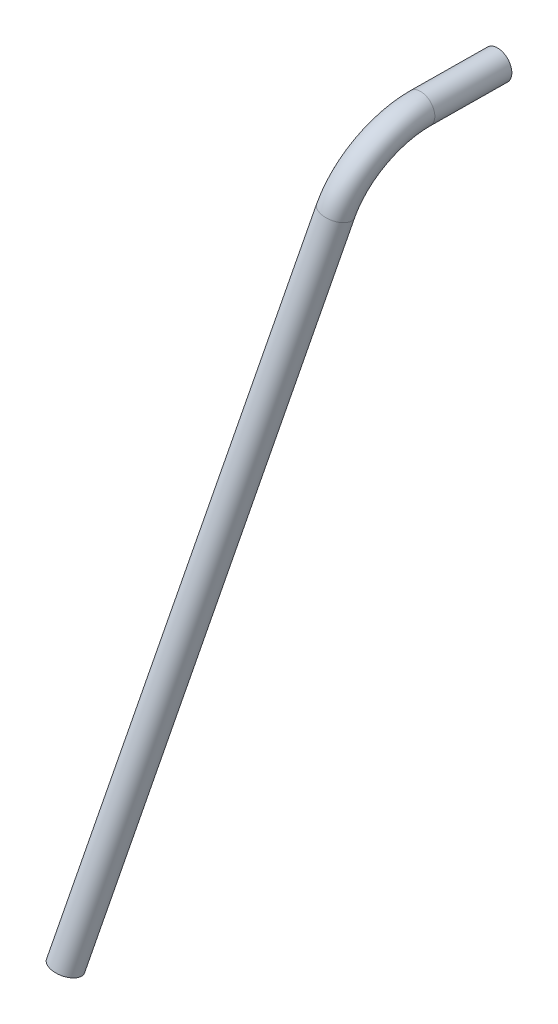
SolidWorks part; units mm, degrees
material "Silicon Rubber"
ref_plane "X-Y Datum" through (0, 0, 0) normal (0, 0, 1) x (1, 0, 0)
ref_plane "X-Z Datum" through (0, 0, 0) normal (0, 1, 0) x (1, 0, 0)
ref_plane "Y-Z Datum" through (0, 0, 0) normal (1, 0, 0) x (0, 0, -1)
sketch3d "3DSketch1"
  line L0 (224.1379, 49.8486, -283.6466) -> (167.4145, -265.9267, -205.541)
  line L1 (229.5393, 78.432, -320.6684) -> (229.8675, 78.3691, -358.7669)
  line L2 (229.5393, 78.432, -320.6684) -> (229.8675, 78.3691, -358.7669) construction
  line L4 (229.5393, 78.432, -320.6684) -> (229.8675, 78.3691, -358.7669) construction
  circle A4 centre (229.5393, 78.432, -320.6684) radius 2.125 construction
  arc A10 (229.5393, 78.432, -320.6684) -> (224.1379, 49.8486, -283.6466) centre (222.8831, 40.9179, -320.6639) ccw
  spline S0 degree 3 poles (229.8159, 70.7981, -321.7901) (228.8067, 70.8296, -321.7989) (228.3104, 70.8947, -321.8136) (227.5781, 71.0652, -321.85) (227.3349, 71.1346, -321.8647) (226.8609, 71.2957, -321.8979) (226.6296, 71.3874, -321.9165) (225.952, 71.6947, -321.9775) (225.522, 71.9425, -322.025) (224.7067, 72.5269, -322.1293) (224.3335, 72.855, -322.1846) (223.826, 73.3966, -322.2672) (223.6654, 73.5856, -322.2948) (223.3618, 73.9808, -322.3491) (223.2183, 74.1879, -322.376) (222.8233, 74.8228, -322.4527) (222.6038, 75.2673, -322.4992) (222.252, 76.1992, -322.5778) (222.1202, 76.6895, -322.6098) (221.9574, 77.6719, -322.6528) (221.924, 78.1688, -322.6643) (221.9481, 78.9231, -322.6653) (221.9687, 79.1748, -322.6628) (222.0337, 79.67, -322.6527) (222.1227, 80.1596, -322.6373) (222.2588, 80.6382, -322.6121) (222.4188, 81.1112, -322.5822) (222.5114, 81.3462, -322.5648) (222.821, 82.0304, -322.5074) (223.0688, 82.4598, -322.4619) (223.6453, 83.2669, -322.3623) (223.9781, 83.6476, -322.3075) (224.7018, 84.3273, -322.1989) (225.0938, 84.6295, -322.1448) (225.7279, 85.0258, -322.0683) (225.948, 85.1488, -322.0434) (226.3953, 85.3704, -321.9969) (226.6232, 85.4696, -321.9752) (227.3195, 85.7331, -321.9152) (227.8022, 85.864, -321.882) (228.7951, 86.0294, -321.834) (229.2922, 86.062, -321.8198) (230.0388, 86.0384, -321.8134) (230.2878, 86.0184, -321.8137) (230.7862, 85.9532, -321.8195) (231.035, 85.908, -321.8249) (231.7648, 85.738, -321.8481) (232.2353, 85.5784, -321.8728) (232.9171, 85.2702, -321.9212) (233.1415, 85.1552, -321.9393) (233.5756, 84.9049, -321.9784) (233.7849, 84.77, -321.9992) (234.3902, 84.337, -322.0646) (234.7639, 84.0108, -322.1121) (235.2785, 83.4633, -322.185) (235.4412, 83.2721, -322.2095) (235.7447, 82.878, -322.2571) (235.8862, 82.6744, -322.2804) (236.149, 82.2539, -322.3254) (236.2703, 82.0371, -322.347) (236.4923, 81.5899, -322.3879) (236.5934, 81.3584, -322.4072) (236.8592, 80.6565, -322.4595) (236.9888, 80.1765, -322.487) (237.1536, 79.1925, -322.5242) (237.1876, 78.6848, -322.5337) (237.1559, 77.6884, -322.5322) (237.0917, 77.1949, -322.5216) (236.9212, 76.4617, -322.4914) (236.8518, 76.2186, -322.479) (236.6912, 75.7458, -322.4503) (236.5083, 75.2835, -322.4178) (236.2817, 74.842, -322.3786) (236.033, 74.4108, -322.3366) (235.8969, 74.1995, -322.3141) (235.4592, 73.5886, -322.2442) (235.1321, 73.216, -322.1949) (234.5898, 72.7071, -322.1213) (234.4003, 72.5458, -322.0968) (234.0035, 72.2405, -322.0487) (233.7969, 72.0972, -322.0252) (233.1632, 71.7022, -321.9584) (232.7186, 71.4819, -321.9185) (232.0179, 71.2164, -321.8693) (231.7773, 71.1386, -321.8546) (231.2934, 71.0081, -321.8297) (231.0497, 70.9551, -321.8196) (230.3134, 70.8322, -321.7962) (229.8159, 70.7981, -321.7901) (228.8067, 70.8296, -321.7989) (228.3104, 70.8947, -321.8136) knots -0.03125 -0.03125 0 0 0.03125 0.03125 0.046875 0.046875 0.0625 0.0625 0.09375 0.09375 0.125 0.125 0.140625 0.140625 0.15625 0.15625 0.1875 0.1875 0.21875 0.21875 0.25 0.25 0.265625 0.265625 0.28125 0.296875 0.296875 0.3125 0.3125 0.34375 0.34375 0.375 0.375 0.40625 0.40625 0.421875 0.421875 0.4375 0.4375 0.46875 0.46875 0.5 0.5 0.515625 0.515625 0.53125 0.53125 0.5625 0.5625 0.578125 0.578125 0.59375 0.59375 0.625 0.625 0.640625 0.640625 0.65625 0.65625 0.671875 0.671875 0.6875 0.6875 0.71875 0.71875 0.75 0.75 0.78125 0.78125 0.796875 0.796875 0.8125 0.828125 0.828125 0.84375 0.84375 0.875 0.875 0.890625 0.890625 0.90625 0.90625 0.9375 0.9375 0.953125 0.953125 0.96875 0.96875 1 1 1.03125 1.03125 1.046875 only from (229.3113, 70.8138, -321.7945) to (229.3113, 70.8138, -321.7945) construction
  spline S1 degree 3 poles (221.9365, 78.1593, -324.0996) (221.968, 79.1688, -324.101) (222.0331, 79.6652, -324.0903) (222.2033, 80.3977, -324.0583) (222.2727, 80.641, -324.0449) (222.4336, 81.1155, -324.0137) (222.5252, 81.3471, -323.9958) (222.8321, 82.0253, -323.9365) (223.0795, 82.4555, -323.8894) (223.6626, 83.2712, -323.7847) (223.9907, 83.6455, -323.7286) (224.5316, 84.1537, -323.6443) (224.7202, 84.3144, -323.6161) (225.1148, 84.6185, -323.5604) (225.3217, 84.7622, -323.5327) (225.9562, 85.1583, -323.4533) (226.4005, 85.3783, -323.4048) (227.3316, 85.7309, -323.3216) (227.8218, 85.8631, -323.2869) (228.8042, 86.0264, -323.2379) (229.3011, 86.0599, -323.2231) (230.0552, 86.0359, -323.2166) (230.3072, 86.0153, -323.2172) (230.8027, 85.9501, -323.2234) (231.2926, 85.8609, -323.2347) (231.7713, 85.7245, -323.2557) (232.2444, 85.5642, -323.2813) (232.4794, 85.4715, -323.2964) (233.1644, 85.1611, -323.3473) (233.5941, 84.9128, -323.3884) (234.4015, 84.3354, -323.4794) (234.7825, 84.0021, -323.53) (235.4629, 83.2773, -323.6306) (235.7654, 82.8849, -323.6809) (236.162, 82.2504, -323.7517) (236.2851, 82.0301, -323.7746) (236.5071, 81.5822, -323.8173) (236.6064, 81.3541, -323.8371) (236.8704, 80.6572, -323.8913) (237.0014, 80.1745, -323.9203) (237.1672, 79.1808, -323.9595) (237.1999, 78.6835, -323.969) (237.1763, 77.9367, -323.9679) (237.1562, 77.6877, -323.965) (237.091, 77.1894, -323.9539) (237.0457, 76.9406, -323.9457) (236.8753, 76.2108, -323.9144) (236.7156, 75.7407, -323.8842) (236.407, 75.0596, -323.8279) (236.2919, 74.8355, -323.8071) (236.0413, 74.4018, -323.763) (235.9062, 74.1928, -323.7398) (235.4727, 73.5883, -323.6677) (235.1463, 73.2152, -323.6163) (234.5985, 72.7016, -323.5388) (234.4071, 72.5391, -323.5131) (234.0127, 72.2361, -323.4633) (233.8089, 72.0948, -323.4391) (233.3881, 71.8325, -323.3929) (233.1711, 71.7114, -323.3708) (232.7238, 71.4898, -323.3296) (232.4921, 71.3889, -323.3103) (231.7897, 71.1235, -323.2589) (231.3094, 70.9942, -323.2327) (230.3251, 70.8298, -323.1999) (229.8171, 70.7958, -323.1935) (228.8205, 70.8275, -323.2022) (228.327, 70.8917, -323.2171) (227.5941, 71.0618, -323.2547) (227.3509, 71.1311, -323.2698) (226.8783, 71.2915, -323.304) (226.6472, 71.3828, -323.3232) (226.1956, 71.5872, -323.3652) (225.975, 71.7003, -323.3881) (225.5442, 71.9486, -323.4368) (225.3331, 72.0844, -323.4628) (224.7228, 72.5214, -323.5437) (224.3507, 72.848, -323.6008) (223.8425, 73.3894, -323.6866) (223.6815, 73.5786, -323.7153) (223.3767, 73.9747, -323.7719) (223.2336, 74.1811, -323.7997) (222.8392, 74.8139, -323.8792) (222.6192, 75.258, -323.9275) (222.3542, 75.9581, -323.989) (222.2765, 76.1985, -324.0077) (222.1461, 76.6822, -324.0401) (222.0933, 76.9258, -324.0539) (221.9706, 77.6618, -324.0875) (221.9365, 78.1593, -324.0996) (221.968, 79.1688, -324.101) (222.0331, 79.6652, -324.0903) knots -0.03125 -0.03125 0 0 0.03125 0.03125 0.046875 0.046875 0.0625 0.0625 0.09375 0.09375 0.125 0.125 0.140625 0.140625 0.15625 0.15625 0.1875 0.1875 0.21875 0.21875 0.25 0.25 0.265625 0.265625 0.28125 0.296875 0.296875 0.3125 0.3125 0.34375 0.34375 0.375 0.375 0.40625 0.40625 0.421875 0.421875 0.4375 0.4375 0.46875 0.46875 0.5 0.5 0.515625 0.515625 0.53125 0.53125 0.5625 0.5625 0.578125 0.578125 0.59375 0.59375 0.625 0.625 0.640625 0.640625 0.65625 0.65625 0.671875 0.671875 0.6875 0.6875 0.71875 0.71875 0.75 0.75 0.78125 0.78125 0.796875 0.796875 0.8125 0.8125 0.828125 0.828125 0.84375 0.84375 0.875 0.875 0.890625 0.890625 0.90625 0.90625 0.9375 0.9375 0.953125 0.953125 0.96875 0.96875 1 1 1.03125 1.03125 1.046875 only from (221.9523, 78.6641, -324.1003) to (221.9523, 78.6641, -324.1003) construction
  spline S2 degree 3 poles (229.8159, 70.7981, -321.7901) (228.8067, 70.8296, -321.7989) (228.3104, 70.8947, -321.8136) (227.5781, 71.0652, -321.85) (227.3349, 71.1346, -321.8647) (226.8609, 71.2957, -321.8979) (226.6296, 71.3874, -321.9165) (225.952, 71.6947, -321.9775) (225.522, 71.9425, -322.025) (224.7067, 72.5269, -322.1293) (224.3335, 72.855, -322.1846) (223.826, 73.3966, -322.2672) (223.6654, 73.5856, -322.2948) (223.3618, 73.9808, -322.3491) (223.2183, 74.1879, -322.376) (222.8233, 74.8228, -322.4527) (222.6038, 75.2673, -322.4992) (222.252, 76.1992, -322.5778) (222.1202, 76.6895, -322.6098) (221.9574, 77.6719, -322.6528) (221.924, 78.1688, -322.6643) (221.9481, 78.9231, -322.6653) (221.9687, 79.1748, -322.6628) (222.0337, 79.67, -322.6527) (222.1227, 80.1596, -322.6373) (222.2588, 80.6382, -322.6121) (222.4188, 81.1112, -322.5822) (222.5114, 81.3462, -322.5648) (222.821, 82.0304, -322.5074) (223.0688, 82.4598, -322.4619) (223.6453, 83.2669, -322.3623) (223.9781, 83.6476, -322.3075) (224.7018, 84.3273, -322.1989) (225.0938, 84.6295, -322.1448) (225.7279, 85.0258, -322.0683) (225.948, 85.1488, -322.0434) (226.3953, 85.3704, -321.9969) (226.6232, 85.4696, -321.9752) (227.3195, 85.7331, -321.9152) (227.8022, 85.864, -321.882) (228.7951, 86.0294, -321.834) (229.2922, 86.062, -321.8198) (230.0388, 86.0384, -321.8134) (230.2878, 86.0184, -321.8137) (230.7862, 85.9532, -321.8195) (231.035, 85.908, -321.8249) (231.7648, 85.738, -321.8481) (232.2353, 85.5784, -321.8728) (232.9171, 85.2702, -321.9212) (233.1415, 85.1552, -321.9393) (233.5756, 84.9049, -321.9784) (233.7849, 84.77, -321.9992) (234.3902, 84.337, -322.0646) (234.7639, 84.0108, -322.1121) (235.2785, 83.4633, -322.185) (235.4412, 83.2721, -322.2095) (235.7447, 82.878, -322.2571) (235.8862, 82.6744, -322.2804) (236.149, 82.2539, -322.3254) (236.2703, 82.0371, -322.347) (236.4923, 81.5899, -322.3879) (236.5934, 81.3584, -322.4072) (236.8592, 80.6565, -322.4595) (236.9888, 80.1765, -322.487) (237.1536, 79.1925, -322.5242) (237.1876, 78.6848, -322.5337) (237.1559, 77.6884, -322.5322) (237.0917, 77.1949, -322.5216) (236.9212, 76.4617, -322.4914) (236.8518, 76.2186, -322.479) (236.6912, 75.7458, -322.4503) (236.5083, 75.2835, -322.4178) (236.2817, 74.842, -322.3786) (236.033, 74.4108, -322.3366) (235.8969, 74.1995, -322.3141) (235.4592, 73.5886, -322.2442) (235.1321, 73.216, -322.1949) (234.5898, 72.7071, -322.1213) (234.4003, 72.5458, -322.0968) (234.0035, 72.2405, -322.0487) (233.7969, 72.0972, -322.0252) (233.1632, 71.7022, -321.9584) (232.7186, 71.4819, -321.9185) (232.0179, 71.2164, -321.8693) (231.7773, 71.1386, -321.8546) (231.2934, 71.0081, -321.8297) (231.0497, 70.9551, -321.8196) (230.3134, 70.8322, -321.7962) (229.8159, 70.7981, -321.7901) (228.8067, 70.8296, -321.7989) (228.3104, 70.8947, -321.8136) knots -0.03125 -0.03125 0 0 0.03125 0.03125 0.046875 0.046875 0.0625 0.0625 0.09375 0.09375 0.125 0.125 0.140625 0.140625 0.15625 0.15625 0.1875 0.1875 0.21875 0.21875 0.25 0.25 0.265625 0.265625 0.28125 0.296875 0.296875 0.3125 0.3125 0.34375 0.34375 0.375 0.375 0.40625 0.40625 0.421875 0.421875 0.4375 0.4375 0.46875 0.46875 0.5 0.5 0.515625 0.515625 0.53125 0.53125 0.5625 0.5625 0.578125 0.578125 0.59375 0.59375 0.625 0.625 0.640625 0.640625 0.65625 0.65625 0.671875 0.671875 0.6875 0.6875 0.71875 0.71875 0.75 0.75 0.78125 0.78125 0.796875 0.796875 0.8125 0.828125 0.828125 0.84375 0.84375 0.875 0.875 0.890625 0.890625 0.90625 0.90625 0.9375 0.9375 0.953125 0.953125 0.96875 0.96875 1 1 1.03125 1.03125 1.046875 only from (229.3113, 70.8138, -321.7945) to (229.3113, 70.8138, -321.7945) construction
  spline S3 degree 3 poles (221.9365, 78.1593, -324.0996) (221.968, 79.1688, -324.101) (222.0331, 79.6652, -324.0903) (222.2033, 80.3977, -324.0583) (222.2727, 80.641, -324.0449) (222.4336, 81.1155, -324.0137) (222.5252, 81.3471, -323.9958) (222.8321, 82.0253, -323.9365) (223.0795, 82.4555, -323.8894) (223.6626, 83.2712, -323.7847) (223.9907, 83.6455, -323.7286) (224.5316, 84.1537, -323.6443) (224.7202, 84.3144, -323.6161) (225.1148, 84.6185, -323.5604) (225.3217, 84.7622, -323.5327) (225.9562, 85.1583, -323.4533) (226.4005, 85.3783, -323.4048) (227.3316, 85.7309, -323.3216) (227.8218, 85.8631, -323.2869) (228.8042, 86.0264, -323.2379) (229.3011, 86.0599, -323.2231) (230.0552, 86.0359, -323.2166) (230.3072, 86.0153, -323.2172) (230.8027, 85.9501, -323.2234) (231.2926, 85.8609, -323.2347) (231.7713, 85.7245, -323.2557) (232.2444, 85.5642, -323.2813) (232.4794, 85.4715, -323.2964) (233.1644, 85.1611, -323.3473) (233.5941, 84.9128, -323.3884) (234.4015, 84.3354, -323.4794) (234.7825, 84.0021, -323.53) (235.4629, 83.2773, -323.6306) (235.7654, 82.8849, -323.6809) (236.162, 82.2504, -323.7517) (236.2851, 82.0301, -323.7746) (236.5071, 81.5822, -323.8173) (236.6064, 81.3541, -323.8371) (236.8704, 80.6572, -323.8913) (237.0014, 80.1745, -323.9203) (237.1672, 79.1808, -323.9595) (237.1999, 78.6835, -323.969) (237.1763, 77.9367, -323.9679) (237.1562, 77.6877, -323.965) (237.091, 77.1894, -323.9539) (237.0457, 76.9406, -323.9457) (236.8753, 76.2108, -323.9144) (236.7156, 75.7407, -323.8842) (236.407, 75.0596, -323.8279) (236.2919, 74.8355, -323.8071) (236.0413, 74.4018, -323.763) (235.9062, 74.1928, -323.7398) (235.4727, 73.5883, -323.6677) (235.1463, 73.2152, -323.6163) (234.5985, 72.7016, -323.5388) (234.4071, 72.5391, -323.5131) (234.0127, 72.2361, -323.4633) (233.8089, 72.0948, -323.4391) (233.3881, 71.8325, -323.3929) (233.1711, 71.7114, -323.3708) (232.7238, 71.4898, -323.3296) (232.4921, 71.3889, -323.3103) (231.7897, 71.1235, -323.2589) (231.3094, 70.9942, -323.2327) (230.3251, 70.8298, -323.1999) (229.8171, 70.7958, -323.1935) (228.8205, 70.8275, -323.2022) (228.327, 70.8917, -323.2171) (227.5941, 71.0618, -323.2547) (227.3509, 71.1311, -323.2698) (226.8783, 71.2915, -323.304) (226.6472, 71.3828, -323.3232) (226.1956, 71.5872, -323.3652) (225.975, 71.7003, -323.3881) (225.5442, 71.9486, -323.4368) (225.3331, 72.0844, -323.4628) (224.7228, 72.5214, -323.5437) (224.3507, 72.848, -323.6008) (223.8425, 73.3894, -323.6866) (223.6815, 73.5786, -323.7153) (223.3767, 73.9747, -323.7719) (223.2336, 74.1811, -323.7997) (222.8392, 74.8139, -323.8792) (222.6192, 75.258, -323.9275) (222.3542, 75.9581, -323.989) (222.2765, 76.1985, -324.0077) (222.1461, 76.6822, -324.0401) (222.0933, 76.9258, -324.0539) (221.9706, 77.6618, -324.0875) (221.9365, 78.1593, -324.0996) (221.968, 79.1688, -324.101) (222.0331, 79.6652, -324.0903) knots -0.03125 -0.03125 0 0 0.03125 0.03125 0.046875 0.046875 0.0625 0.0625 0.09375 0.09375 0.125 0.125 0.140625 0.140625 0.15625 0.15625 0.1875 0.1875 0.21875 0.21875 0.25 0.25 0.265625 0.265625 0.28125 0.296875 0.296875 0.3125 0.3125 0.34375 0.34375 0.375 0.375 0.40625 0.40625 0.421875 0.421875 0.4375 0.4375 0.46875 0.46875 0.5 0.5 0.515625 0.515625 0.53125 0.53125 0.5625 0.5625 0.578125 0.578125 0.59375 0.59375 0.625 0.625 0.640625 0.640625 0.65625 0.65625 0.671875 0.671875 0.6875 0.6875 0.71875 0.71875 0.75 0.75 0.78125 0.78125 0.796875 0.796875 0.8125 0.8125 0.828125 0.828125 0.84375 0.84375 0.875 0.875 0.890625 0.890625 0.90625 0.90625 0.9375 0.9375 0.953125 0.953125 0.96875 0.96875 1 1 1.03125 1.03125 1.046875 only from (221.9523, 78.6641, -324.1003) to (221.9523, 78.6641, -324.1003) construction
  point P1 (260.3958, 34.2621, -320.3297)
  point P21 (229.5393, 78.432, -318.5434)
  dimension "D1" = 38.1
  dimension "D2" = 38.1
  dimension "D4" = 330.2
sweep "Sweep1" add path "3DSketch1" circular profile diameter 14.2875 parameters "D3"=14.2875
sweep "Cut-Sweep1" cut path "3DSketch1<2>" circular profile diameter 6.35 parameters "D3"=6.35
sketch3d "3DSketch1<2>" same geometry as "3DSketch1"
